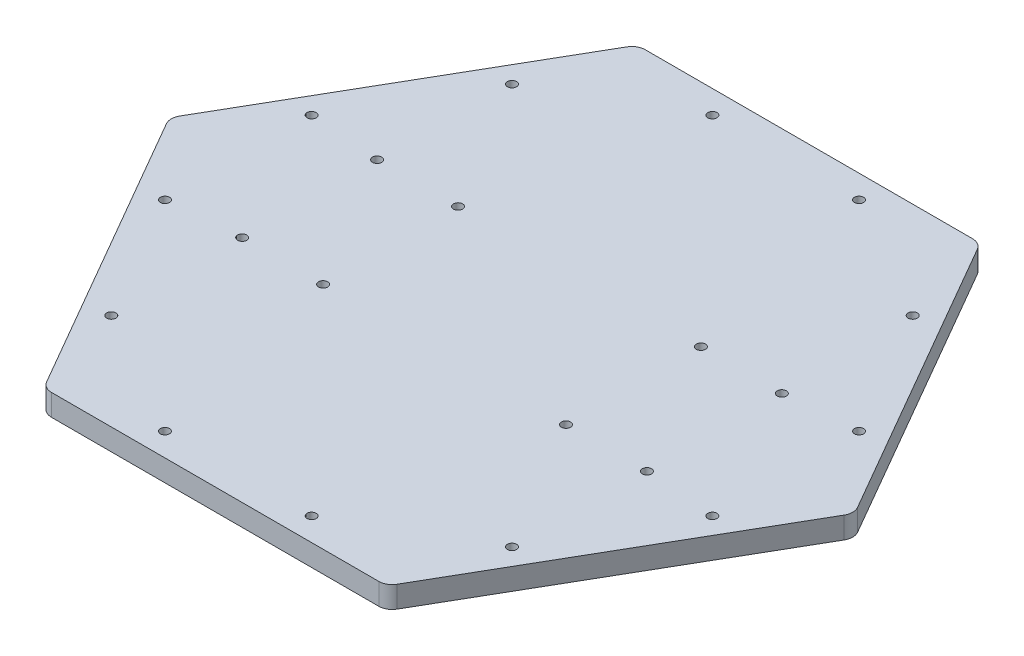
SolidWorks part; units mm, degrees
ref_plane "Front Plane" through (0, 0, 0) normal (0, 0, 1) x (1, 0, 0)
ref_plane "Top Plane" through (0, 0, 0) normal (0, 1, 0) x (1, 0, 0)
ref_plane "Right Plane" through (0, 0, 0) normal (1, 0, 0) x (0, 0, -1)
sketch "Sketch1" plane through (0, 0, 0) normal (0, 1, 0) x (1, 0, 0)
  line L0 (-85, 25) -> (85, 25) construction
  line L1 (127.0171, 0) -> (63.5085, 110)
  line L2 (63.5085, 110) -> (-63.5085, 110)
  line L3 (-63.5085, 110) -> (-127.0171, 0)
  line L4 (-127.0171, 0) -> (-63.5085, -110)
  line L5 (-63.5085, -110) -> (63.5085, -110)
  line L6 (63.5085, -110) -> (127.0171, 0)
  line L7 (-85, 35) -> (85, 35) construction
  line L8 (-85, 35) -> (-85, -35) construction
  line L9 (-85, -35) -> (85, -35) construction
  line L10 (85, 35) -> (85, -35) construction
  line L11 (-85, 35) -> (85, -35) construction
  line L12 (-85, -35) -> (85, 35) construction
  line L13 (-85, -25) -> (85, -25) construction
  line L14 (-75, 35) -> (-75, -35) construction
  line L15 (75, 35) -> (75, -35) construction
  line L16 (-45, 35) -> (-45, -35) construction
  line L17 (45, 35) -> (45, -35) construction
  line L18 (0, 0) -> (-74.2462, -74.2462) construction
  line L19 (0, 0) -> (-63.5085, -110) construction
  circle A0 centre (0, 0) radius 110 construction
  circle A1 centre (-75, 25) radius 1.7
  circle A2 centre (-75, -25) radius 1.7
  circle A3 centre (75, 25) radius 1.7
  circle A4 centre (75, -25) radius 1.7
  circle A5 centre (-45, 25) radius 1.7
  circle A6 centre (-45, -25) radius 1.7
  circle A7 centre (45, 25) radius 1.7
  circle A8 centre (45, -25) radius 1.7
  circle A9 centre (-74.2462, -74.2462) radius 1.7
  circle A10 centre (-101.4222, -27.176) radius 1.7
  circle A11 centre (-101.4222, 27.176) radius 1.7
  circle A12 centre (-74.2462, 74.2462) radius 1.7
  circle A13 centre (-27.176, 101.4222) radius 1.7
  circle A14 centre (27.176, 101.4222) radius 1.7
  circle A15 centre (74.2462, 74.2462) radius 1.7
  circle A16 centre (101.4222, 27.176) radius 1.7
  circle A17 centre (101.4222, -27.176) radius 1.7
  circle A18 centre (74.2462, -74.2462) radius 1.7
  circle A19 centre (27.176, -101.4222) radius 1.7
  circle A20 centre (-27.176, -101.4222) radius 1.7
  point P68 (0, 0)
  dimension "D1" = 220
  dimension "D8" = 30
  dimension "D10" = 105
  dimension "D12" = 12
  dimension "D2" = 170
  dimension "D3" = 70
  dimension "D4" = 10
  dimension "D5" = 10
  dimension "D6" = 10
  dimension "D7" = 10
  dimension "D9" = 30
  dimension "D11" = 15
base flange "Base-Flange1" sketch "Sketch1" thickness 8 reverse thickness direction no parameters "D1"=3
fillet "Fillet2" radius 5 6 edges at (127.0171, -4, 0) (63.5085, -4, -110) (-63.5085, -4, -110) (-127.0171, -4, 0) (-63.5085, -4, 110) (63.5085, -4, 110)
sketch "Bend-Lines1" [suppressed] plane through (0, 0, 0) normal (0, 1, 0) x (1, 0, 0)
sketch "Bounding-Box1" [suppressed] plane through (0, 0, 0) normal (0, 1, 0) x (1, 0, 0)
sheet metal parameters "Sheet-Metal1" thickness 8 parameters "D1"=3
flat pattern "Flat-Pattern1" [suppressed]
sketch "Bend-Lines2" plane through (0, 0, 0) normal (0, 1, 0) x (1, 0, 0)
sketch3d "Bounding-Box2" [suppressed]
  line L0 (126.2435, -110, 0) -> (-126.2435, -110, 0) construction
  line L1 (126.2435, 110, 0) -> (-126.2435, 110, 0) construction
  line L2 (126.2435, -110, 0) -> (126.2435, 110, 0) construction
  line L3 (-126.2435, -110, 0) -> (-126.2435, 110, 0) construction
